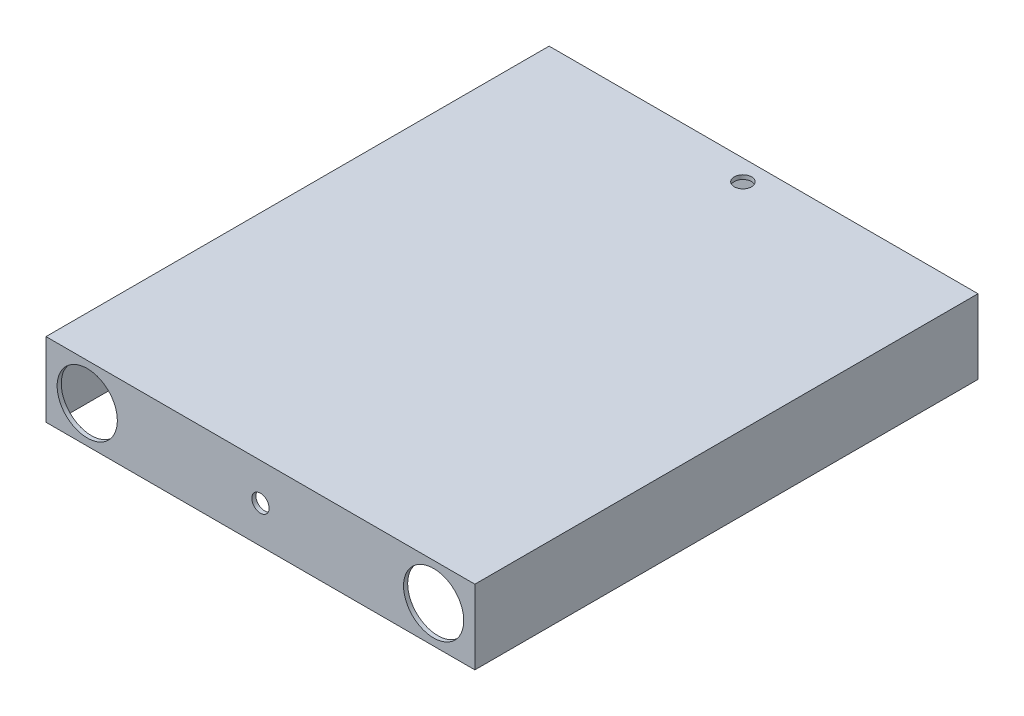
SolidWorks part; units mm, degrees
ref_plane "Front Plane" through (0, 0, 0) normal (0, 0, 1) x (1, 0, 0)
ref_plane "Top Plane" through (0, 0, 0) normal (0, 1, 0) x (1, 0, 0)
ref_plane "Right Plane" through (0, 0, 0) normal (1, 0, 0) x (0, 0, -1)
sketch "Sketch1" plane through (0, 0, 0) normal (0, 1, 0) x (1, 0, 0)
  line L1 (260, -305) -> (-260, -305)
  line L2 (260, -305) -> (260, 305)
  line L3 (260, 305) -> (-260, 305)
  line L4 (-260, -305) -> (-260, 305)
  line L5 (260, -305) -> (-260, 305) construction
  line L6 (260, 305) -> (-260, -305) construction
  point P0 (0, 0)
extrude "Boss-Extrude1" add sketch "Sketch1" along normal mid plane 90
shell "Shell1" thickness 5 removed face at (0, -45, 0)
sketch "Sketch3" plane through (0, 0, 305) normal (0, 0, 1) x (1, 0, 0)
  line L0 (0, 0) -> (-50000, 0) construction
  line L1 (0, 0) -> (0, 50000) construction
  circle A0 centre (-210, 0) radius 36.5
  circle A1 centre (210, 0) radius 36.5
  dimension "D1" = 73
  dimension "D2" = 210
sketch "Sketch4" plane through (0, 45, 0) normal (0, 1, 0) x (1, 0, 0)
  line L0 (260, 305) -> (-260, 305) construction
  circle A0 centre (0, 280) radius 10.5
  dimension "D1" = 21
  dimension "D2" = 25
extrude "Cut-Extrude2" cut sketch "Sketch4" against normal blind 10
sketch "Sketch5" plane through (0, 0, 305) normal (0, 0, 1) x (1, 0, 0)
  circle A0 centre (0, 0) radius 10.5
  dimension "D1" = 21
extrude "Cut-Extrude3" cut sketch "Sketch5" against normal blind 10
extrude "Cut-Extrude4" cut sketch "Sketch3" against normal blind 25
ref_axis "Axis1" through (0, 0, 244.0899) along (0, 0, 1)
ref_axis "Axis2" through (210, 0, 179.596) along (0, 0, 1)
ref_axis "Axis3" through (-210, 0, 269.8344) along (0, 0, 1)
ref_axis "Axis4" through (0, 12.0431, -280) along (0, 1, 0)
